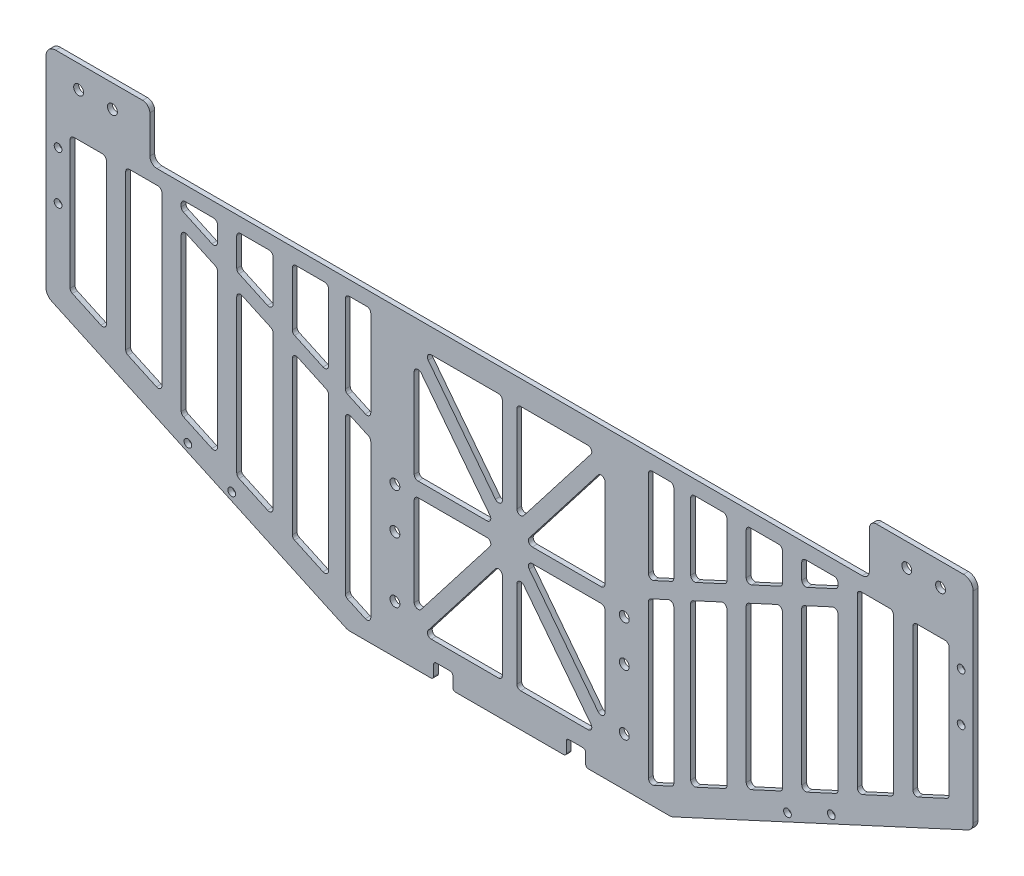
SolidWorks part; units mm, degrees
material "Thornel Mat VMA"
ref_plane "前视基准面" through (0, 0, 0) normal (0, 0, 1) x (1, 0, 0)
ref_plane "上视基准面" through (0, 0, 0) normal (0, 1, 0) x (1, 0, 0)
ref_plane "右视基准面" through (0, 0, 0) normal (1, 0, 0) x (0, 0, -1)
sketch "草图1" plane through (0, 0, 0) normal (0, 0, 1) x (1, 0, 0)
  line L1 (-192, -65) -> (192, -65)
  line L2 (-192, -65) -> (-192, 65)
  line L3 (-192, 65) -> (192, 65)
  line L4 (192, -65) -> (192, 65)
  line L5 (-192, -65) -> (192, 65) construction
  line L6 (-192, 65) -> (192, -65) construction
  point P0 (0, 0)
  dimension "D1" = 130
  dimension "D2" = 384
extrude "凸台-拉伸1" add sketch "草图1" along normal blind 2
sketch "草图2" plane through (0, 0, 2) normal (0, 0, 1) x (1, 0, 0)
  line L0 (192, 65) -> (-192, 65) construction
  line L1 (-145, 61) -> (-127, 61)
  line L2 (-145, 61) -> (-145, 69)
  line L3 (-145, 69) -> (-127, 69)
  line L4 (-127, 61) -> (-127, 69)
  line L5 (-145, 61) -> (-127, 69) construction
  line L6 (-145, 69) -> (-127, 61) construction
  point P0 (-136, 65)
  dimension "D1" = 4
  dimension "D2" = 145
  dimension "D3" = 18
extrude "切除-拉伸1" cut sketch "草图2" against normal blind 3
mirror "镜向1" about plane through (0, 0, 0) normal (1, 0, 0) of "切除-拉伸1"
sketch "草图3" plane through (0, 0, 2) normal (0, 0, 1) x (1, 0, 0)
  line L1 (-127, 61) -> (127, 61)
  line L2 (-127, 61) -> (-127, 65)
  line L3 (-127, 65) -> (127, 65)
  line L4 (127, 61) -> (127, 65)
extrude "切除-拉伸2" cut sketch "草图3" against normal blind 3
sketch "草图4" plane through (0, 0, 2) normal (0, 0, 1) x (1, 0, 0)
  line L0 (67, -65) -> (192, -7.3077)
  line L1 (-192, -65) -> (192, -65) construction
  line L2 (192, -65) -> (192, 65) construction
  line L4 (67, -65) -> (192, -65)
  line L5 (192, -65) -> (192, -7.3077)
  dimension "D1" = 125
  dimension "D2" = 24.775
extrude "切除-拉伸3" cut sketch "草图4" against normal blind 10
mirror "镜向2" about plane through (0, 0, 0) normal (1, 0, 0) of "切除-拉伸3"
sketch "草图5" plane through (0, 0, 2) normal (0, 0, 1) x (1, 0, 0)
  line L0 (0, 0) -> (187, 0) construction
  line L1 (187, 0) -> (187, 28) construction
  line L2 (187, 28) -> (187, 48) construction
  circle A2 centre (187, 28) radius 1.6
  circle A3 centre (187, 48) radius 1.6
  dimension "D4" = 3.2
  dimension "D1" = 187
  dimension "D2" = 28
  dimension "D3" = 20
extrude "切除-拉伸4" cut sketch "草图5" against normal blind 10
mirror "镜向3" about plane through (0, 0, 0) normal (1, 0, 0) of "切除-拉伸4"
sketch "草图6" plane through (0, 0, 0) normal (0, 0, -1) x (-1, 0, 0)
  line L0 (0, 0) -> (0, -39.5048) construction
  line L1 (0, -39.5048) -> (-115.0806, -39.5048) construction
  line L2 (-115.0806, -39.5048) -> (-133.2398, -31.1237) construction
  circle A2 centre (-133.2398, -31.1237) radius 1.6
  circle A3 centre (-115.0806, -39.5048) radius 1.6
  dimension "D5" = 3.2
  dimension "D1" = 155.225
  dimension "D2" = 115.0806
  dimension "D3" = 39.5048
  dimension "D4" = 20
extrude "切除-拉伸5" cut sketch "草图6" against normal blind 10
mirror "镜向4" about plane through (0, 0, 0) normal (1, 0, 0) of "切除-拉伸5"
sketch "草图7" plane through (0, 0, 2) normal (0, 0, 1) x (1, 0, 0)
  line L0 (0, 0) -> (0, -3) construction
  line L1 (0, -3) -> (-47.5, -3) construction
  line L2 (-47.5, -3) -> (-47.5, -20) construction
  line L3 (-47.5, -20) -> (-47.5, -45) construction
  circle A3 centre (-47.5, -45) radius 2.05
  circle A4 centre (-47.5, -20) radius 2.05
  circle A5 centre (-47.5, -3) radius 2.05
  dimension "D5" = 4.1
  dimension "D1" = 47.5
  dimension "D2" = 3
  dimension "D3" = 17
  dimension "D4" = 25
extrude "切除-拉伸6" cut sketch "草图7" against normal blind 10
mirror "镜向5" about plane through (0, 0, 0) normal (1, 0, 0) of "切除-拉伸6"
sketch "草图8" plane through (0, 0, 2) normal (0, 0, 1) x (1, 0, 0)
  line L0 (-182, 55) -> (-182, -0.9094)
  line L1 (-182, -0.9094) -> (-57.5, -58.3709)
  line L2 (-57.5, -58.3709) -> (-57.5, 55)
  line L3 (-57.5, 55) -> (-182, 55)
  line L5 (-145, 65) -> (-192, 65) construction
  line L6 (-192, 65) -> (-192, -7.3077) construction
  line L7 (-192, -7.3077) -> (-67, -65) construction
  line L8 (-167, 55) -> (-167, -7.8324)
  line L9 (-159, 55) -> (-159, -11.5248)
  line L10 (-144, 55) -> (-144, -18.4478)
  line L11 (-136, 55) -> (-136, -22.1401)
  line L12 (-121, 55) -> (-121, -29.0632)
  line L13 (-113, 55) -> (-113, -32.7555)
  line L14 (-98, 55) -> (-98, -39.6786)
  line L15 (-90, 55) -> (-90, -43.3709)
  line L16 (-75, 55) -> (-75, -50.294)
  line L17 (-68, 55) -> (-68, -53.5248)
  circle A0 centre (-47.5, -3) radius 2.05 construction
  dimension "D1" = 10
  dimension "D2" = 10
  dimension "D3" = 10
  dimension "D4" = 10
  dimension "D5" = 15
  dimension "D6" = 8
  dimension "D7" = 15
  dimension "D8" = 8
  dimension "D9" = 15
  dimension "D10" = 8
  dimension "D11" = 15
  dimension "D12" = 8
  dimension "D13" = 15
  dimension "D14" = 7
extrude "切除-拉伸7" cut sketch "草图8" against normal blind 10 contours L8 L3 L0 L1 | L10 L3 L9 L1 | L12 L3 L11 L1 | L14 L3 L13 L1 | L16 L3 L15 L1 | L3 L17 L1 L2 region at (-174.3542, 25.2809, 2) region at (-151.3763, 19.9783, 2) region at (-128.3926, 14.6744, 2) region at (-105.4051, 9.3696, 2) region at (-82.415, 4.0642, 2) region at (-62.7118, -0.4827, 2)
mirror "镜向6" about plane through (0, 0, 0) normal (1, 0, 0) of "切除-拉伸7"
sketch "草图9" plane through (0, 0, 2) normal (0, 0, 1) x (1, 0, 0)
  line L0 (-145, 61) -> (145, 61) construction
  line L1 (-39.5, -51) -> (39.5, -51)
  line L2 (-39.5, -51) -> (-39.5, 51)
  line L3 (-39.5, 51) -> (39.5, 51)
  line L4 (39.5, -51) -> (39.5, 51)
  line L5 (-39.5, -51) -> (39.5, 51) construction
  line L6 (-39.5, 51) -> (39.5, -51) construction
  line L7 (-37.1282, -52.837) -> (41.8718, 49.163)
  line L8 (-41.8718, 49.163) -> (37.1282, -52.837)
  line L9 (-41.8718, -49.163) -> (37.1282, 52.837)
  line L10 (-37.1282, 52.837) -> (41.8718, -49.163)
  line L11 (-39.5, 0) -> (39.5, 0) construction
  line L12 (-39.5, -3) -> (39.5, -3)
  line L13 (-39.5, 3) -> (39.5, 3)
  line L14 (0, 51) -> (0, -51) construction
  line L15 (-3, 51) -> (-3, -51)
  line L16 (3, 51) -> (3, -51)
  circle A0 centre (-47.5, -3) radius 2.05 construction
  point P0 (0, 0)
  dimension "D1" = 10
  dimension "D2" = 8
  dimension "D3" = 3
  dimension "D4" = 3
  dimension "D5" = 3
  dimension "D6" = 3
  dimension "D7" = 3
  dimension "D8" = 3
extrude "切除-拉伸8" cut sketch "草图9" against normal blind 10 contours L15 L7 L1 | L8 L16 L1 | L12 L10 L4 | L7 L13 L4 | L3 L16 L9 | L15 L3 L10 | L2 L13 L8 | L12 L2 L9 region at (-13.9018, -36.9242, 2) region at (13.9018, -36.9242, 2) region at (-28.3727, -17.3669, 2) region at (28.3727, -17.3669, 2) region at (-28.3727, 17.3669, 2) region at (28.3727, 17.3669, 2) region at (-13.9018, 36.9242, 2) region at (13.9018, 36.9242, 2)
sketch "草图10" plane through (0, 0, 2) normal (0, 0, 1) x (1, 0, 0)
  line L0 (-144, 55) -> (-57.5, 15.0769)
  line L1 (-57.5, -58.3709) -> (-57.5, 55) construction
  line L2 (-144, 55) -> (-136, 55) construction
  line L3 (-192, -7.3077) -> (-67, -65) construction
  line L4 (-144, 48.3918) -> (-57.5, 8.4687)
  line L5 (-146.5143, 49.5522) -> (-60.0143, 9.6292) construction
  line L6 (-144, 55) -> (-144, -18.4478) construction
  line L7 (-144, 55) -> (-144, 48.3918)
  line L8 (-57.5, 15.0769) -> (-57.5, 8.4687)
  dimension "D1" = 6
extrude "凸台-拉伸2" add sketch "草图10" against normal up to surface (2 mm away) up to face at (174.5, 25.3145, 0)
mirror "镜向7" about plane through (0, 0, 0) normal (1, 0, 0) of "凸台-拉伸2"
fillet "圆角1" radius 1.6 104 edges at (-39.5, -46.1007, 1) (-39.5, -3, 1) (-6.1181, -3, 1) (-35.7054, 51, 1) (-3, 51, 1) (-3, 8.7727, 1) (-6.1181, 3, 1) (-39.5, 3, 1) (-39.5, 46.1007, 1) (39.5, 3, 1) (6.1181, 3, 1) (39.5, 46.1007, 1) (3, 8.7727, 1) (3, 51, 1) (35.7054, 51, 1) (3, -51, 1) (3, -8.7727, 1) (35.7054, -51, 1) (39.5, -46.1007, 1) (6.1181, -3, 1) (39.5, -3, 1) (-35.7054, -51, 1) (-3, -8.7727, 1) (-3, -51, 1) (-182, -0.9094, 1) (-182, 55, 1) (-167, 55, 1) (-167, -7.8324, 1) (167, 55, 1) (182, 55, 1) (182, -0.9094, 1) (167, -7.8324, 1) (-57.5, 8.4687, 1) (-57.5, -58.3709, 1) (-68, -53.5248, 1) (-68, 13.3149, 1) (-68, 55, 1) (-68, 19.9231, 1) (-90, 55, 1) (-75, 55, 1) (-75, 23.1538, 1) (-90, 30.0769, 1) (-113, 55, 1) (-98, 55, 1) (-98, 33.7692, 1) (-113, 40.6923, 1) (-136, 55, 1) (-121, 55, 1) (-121, 44.3846, 1) (-136, 51.3077, 1) (-144, -18.4478, 1) (-159, -11.5248, 1) (-159, 55, 1) (-144, 55, 1) (-121, -29.0632, 1) (-136, -22.1401, 1) (-136, 44.6995, 1) (-121, 37.7764, 1) (-98, -39.6786, 1) (-113, -32.7555, 1) (-113, 34.0841, 1) (-98, 27.161, 1) (-75, -50.294, 1) (-90, -43.3709, 1) (-90, 23.4687, 1) (-75, 16.5456, 1) (68, -53.5248, 1) (57.5, -58.3709, 1) (57.5, 8.4687, 1) (68, 13.3149, 1) (57.5, 15.0769, 1) (57.5, 55, 1) (68, 55, 1) (68, 19.9231, 1) (75, 23.1538, 1) (75, 55, 1) (90, 55, 1) (90, 30.0769, 1) (98, 33.7692, 1) (98, 55, 1) (113, 55, 1) (113, 40.6923, 1) (121, 44.3846, 1) (121, 55, 1) (136, 55, 1) (136, 51.3077, 1) (159, 55, 1) (159, -11.5248, 1) (144, -18.4478, 1) (144, 55, 1) (136, 44.6995, 1) (136, -22.1401, 1) (121, -29.0632, 1) (121, 37.7764, 1) (113, 34.0841, 1) (113, -32.7555, 1) (98, -39.6786, 1) (98, 27.161, 1) (90, 23.4687, 1) (90, -43.3709, 1) (75, -50.294, 1) (75, 16.5456, 1) (-57.5, 15.0769, 1) (-57.5, 55, 1)
sketch "草图11" plane through (0, 0, 0) normal (0, 0, -1) x (-1, 0, 0)
  line L0 (-145, 61) -> (-145, 65) construction
  line L1 (-192, 65) -> (-145, 65)
  line L2 (-192, 65) -> (-192, 82.5)
  line L3 (-192, 82.5) -> (-145, 82.5)
  line L4 (-145, 65) -> (-145, 82.5)
  dimension "D1" = 17.5
extrude "凸台-拉伸3" add sketch "草图11" against normal up to surface (2 mm away) up to face at (82.5, -13.4126, 2)
mirror "镜向8" about plane through (0, 0, 0) normal (1, 0, 0) of "凸台-拉伸3"
fillet "圆角2" radius 4 10 edges at (67, -65, 1) (192, -7.3077, 1) (-145, 61, 1) (-145, 82.5, 1) (-192, 82.5, 1) (-192, -7.3077, 1) (-67, -65, 1) (145, 61, 1) (145, 82.5, 1) (192, 82.5, 1)
sketch "草图13" plane through (0, 0, 0) normal (0, 0, -1) x (-1, 0, 0)
  line L0 (0, 0) -> (0, 73) construction
  line L1 (0, 73) -> (164.5, 73) construction
  line L2 (164.5, 73) -> (178.5, 73) construction
  line L3 (149, 82.5) -> (188, 82.5) construction
  circle A2 centre (178.5, 73) radius 2.05
  circle A3 centre (164.5, 73) radius 2.05
  dimension "D4" = 4.1
  dimension "D1" = 9.5
  dimension "D2" = 164.5
  dimension "D3" = 14
extrude "切除-拉伸10" cut sketch "草图13" against normal blind 10
mirror "镜向10" about plane through (0, 0, 0) normal (1, 0, 0) of "切除-拉伸10"
sketch "草图14" plane through (0, 0, 0) normal (0, 0, -1) x (-1, 0, 0)
  line L0 (-27.5, -65) -> (27.5, -65) construction
  line L1 (66.1215, -65) -> (-66.1215, -65) construction
  line L2 (0, 0) -> (0, -65) construction
  line L4 (23.5, -71.5) -> (31.5, -71.5)
  line L5 (23.5, -71.5) -> (23.5, -58.5)
  line L6 (23.5, -58.5) -> (31.5, -58.5)
  line L7 (31.5, -71.5) -> (31.5, -58.5)
  line L8 (27.5, -58.5) -> (27.5, -71.5) construction
  line L9 (23.5, -65) -> (31.5, -65) construction
  line L10 (-31.5, -71.5) -> (-23.5, -71.5)
  line L11 (-31.5, -71.5) -> (-31.5, -58.5)
  line L12 (-31.5, -58.5) -> (-23.5, -58.5)
  line L13 (-23.5, -71.5) -> (-23.5, -58.5)
  line L14 (-27.5, -58.5) -> (-27.5, -71.5) construction
  line L15 (-31.5, -65) -> (-23.5, -65) construction
  point P5 (0, -65)
  dimension "D1" = 55
  dimension "D2" = 8
  dimension "D3" = 6.5
extrude "切除-拉伸11" cut sketch "草图14" against normal blind 10
fillet "圆角4" radius 1.1 8 edges at (-23.5, -65, 1) (-23.5, -58.5, 1) (-31.5, -58.5, 1) (-31.5, -65, 1) (23.5, -58.5, 1) (23.5, -65, 1) (31.5, -58.5, 1) (31.5, -65, 1)
sketch "草图15" plane through (0, 0, 2) normal (0, 0, 1) x (1, 0, 0)
  line L0 (-149, 82.5) -> (-149, 61)
  line L1 (-149, 61) -> (-141, 61)
  line L2 (-149, 82.5) -> (-141, 82.5)
  line L3 (-141, 82.5) -> (-141, 61)
  line L4 (0, 0) -> (0, 110.3679) construction
  line L5 (141, 82.5) -> (141, 61)
  line L6 (149, 82.5) -> (141, 82.5)
  line L7 (149, 61) -> (141, 61)
  line L8 (149, 82.5) -> (149, 61)
extrude "切除-拉伸12" cut sketch "草图15" against normal blind 10
fillet "圆角5" radius 3 4 edges at (149, 82.5, 1) (149, 61, 1) (-149, 61, 1) (-149, 82.5, 1)
